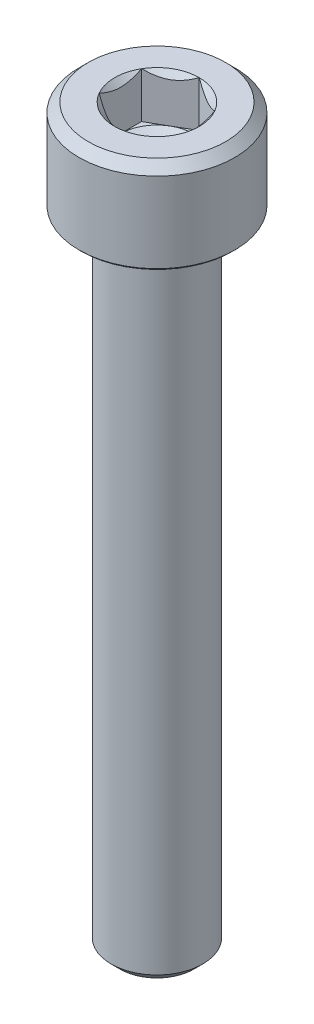
SolidWorks part; units mm, degrees
ref_plane "Front Plane" through (0, 0, 0) normal (0, 0, 1) x (1, 0, 0)
ref_plane "Top Plane" through (0, 0, 0) normal (0, 1, 0) x (1, 0, 0)
ref_plane "Right Plane" through (0, 0, 0) normal (1, 0, 0) x (0, 0, -1)
sketch "Sketch1" plane through (0, 0, 0) normal (0, 0, 1) x (1, 0, 0)
  line L0 (0, 1.3453) -> (2, 2.5)
  line L1 (2, 2.5) -> (2, 4.6906)
  line L2 (2, 4.6906) -> (2.3094, 5)
  line L3 (2.3094, 5) -> (3.75, 5)
  line L4 (3.75, 5) -> (4.25, 4.5)
  line L5 (4.25, 4.5) -> (4.25, 0.125)
  line L6 (4.25, 0.125) -> (4.125, 0)
  line L7 (4.125, 0) -> (2.55, 0)
  line L8 (2.55, 0) -> (2.5, -0.6)
  line L9 (2.5, -0.6) -> (2.5, -34.5095)
  line L10 (2.5, -34.5095) -> (2.0095, -35)
  line L11 (2.0095, -35) -> (0, -35)
  line L12 (0, -35) -> (0, 1.3453)
  line L13 (0, -35) -> (0, 5) construction
revolve "Revolve1" add sketch "Sketch1" angle 360 about L13 reverse direction yes
cosmetic thread "Cosmetic Thread1" parameters "D1"=22, "D2"=4.019
ref_plane "Plane1" through (0, 5, 0) normal (0, 1, 0) x (1, 0, 0)
sketch "Sketch2" plane through (0, 5, 0) normal (0, 1, 0) x (1, 0, 0)
  line L0 (-2, -1.1547) -> (0, -2.3094)
  line L1 (0, -2.3094) -> (2, -1.1547)
  line L2 (2, -1.1547) -> (2, 1.1547)
  line L3 (2, 1.1547) -> (0, 2.3094)
  line L4 (0, 2.3094) -> (-2, 1.1547)
  line L5 (-2, 1.1547) -> (-2, -1.1547)
extrude "Cut-Extrude1" cut sketch "Sketch2" against normal blind 2.5
ref_plane "Plane2" through (0, -35, 0) normal (0, 1, 0) x (1, 0, 0)
ref_plane "ANBAU XY" through (0, 0, 0) normal (0, 1, 0) x (1, 0, 0)
ref_plane "ANBAU XZ" through (0, 0, 0) normal (0, 0, 1) x (1, 0, 0)
ref_plane "ANBAU YZ" through (0, 0, 0) normal (1, 0, 0) x (0, 0, -1)
ref_axis "ANBAU X" through (-80.9, 0, 0) along (1, 0, 0)
ref_axis "ANBAU Y" through (0, 0, 50) along (0, 0, -1)
ref_axis "ANBAU Z" through (0, 50, 0) along (0, -1, 0)
sketch3d "ANBAU"
  point P0 (0, 0, 0)
ref_plane "Schraube XY" through (0, 0, 0) normal (0, 1, 0) x (1, 0, 0)
ref_plane "Schraube XZ" through (0, 0, 0) normal (0, 0, 1) x (1, 0, 0)
ref_plane "Schraube YZ" through (0, 0, 0) normal (1, 0, 0) x (0, 0, -1)
ref_axis "Schraube X" through (-80.9, 0, 0) along (1, 0, 0)
ref_axis "Schraube Y" through (0, 0, 50) along (0, 0, -1)
ref_axis "Schraube Z" through (0, 50, 0) along (0, -1, 0)
sketch3d "Schraube"
  point P0 (0, 0, 0)
ref_plane "insert XY" through (0, 0, 0) normal (0, 1, 0) x (1, 0, 0)
ref_plane "insert XZ" through (0, 0, 0) normal (0, 0, 1) x (1, 0, 0)
ref_plane "insert YZ" through (0, 0, 0) normal (1, 0, 0) x (0, 0, -1)
ref_axis "insert X" through (-80.9, 0, 0) along (1, 0, 0)
ref_axis "insert Y" through (0, 0, 50) along (0, 0, -1)
ref_axis "insert Z" through (0, 50, 0) along (0, -1, 0)
sketch3d "insert"
  point P0 (0, 0, 0)
ref_plane "schrauben_punkt XY" through (0, -35, 0) normal (0, 1, 0) x (1, 0, 0)
ref_plane "schrauben_punkt XZ" through (0, 0, 0) normal (0, 0, 1) x (1, 0, 0)
ref_plane "schrauben_punkt YZ" through (0, 0, 0) normal (1, 0, 0) x (0, 0, -1)
ref_axis "schrauben_punkt X" through (-80.9, -35, 0) along (1, 0, 0)
ref_axis "schrauben_punkt Y" through (0, -35, 50) along (0, 0, -1)
ref_axis "schrauben_punkt Z" through (0, 50, 0) along (0, -1, 0)
sketch3d "schrauben_punkt"
  point P0 (0, -35, 0)
other "Freeze***"
